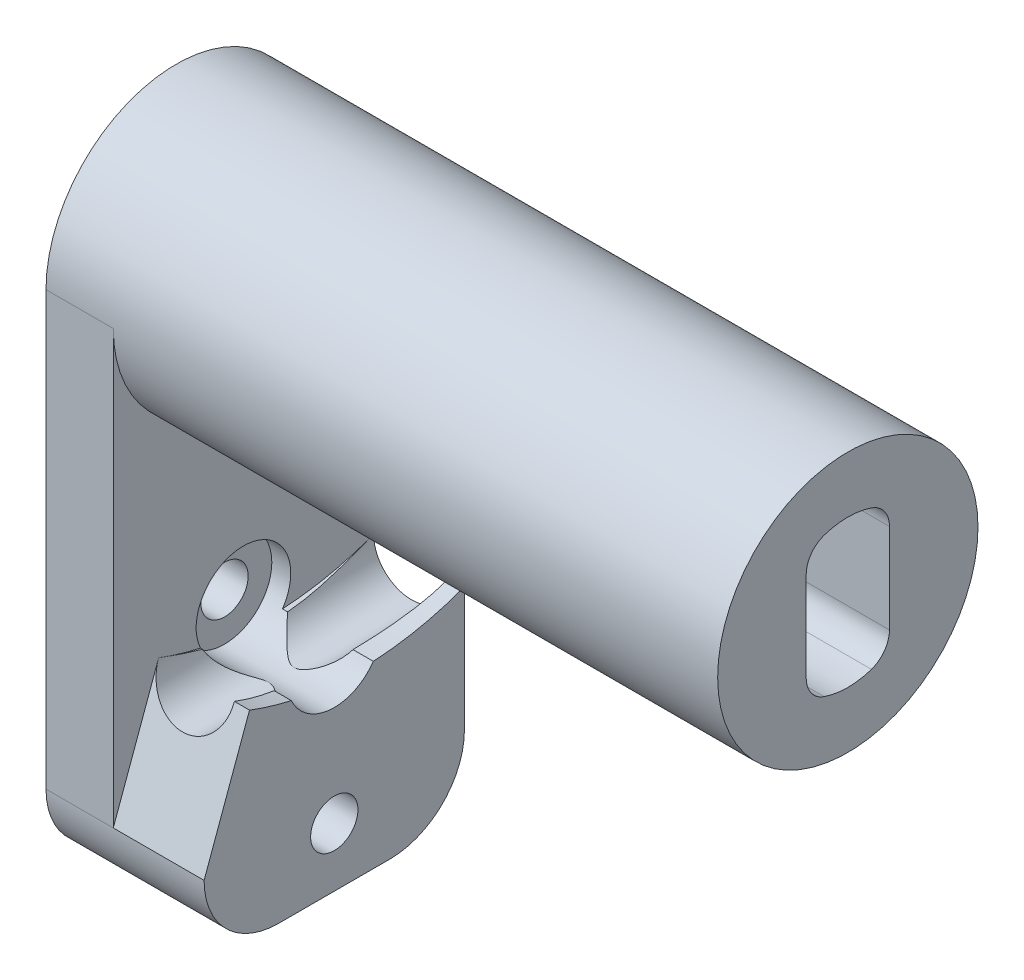
SolidWorks part; units mm, degrees
material "ABS"
ref_plane "Front Plane" through (0, 0, 0) normal (1, 0, 0) x (0, 1, 0)
ref_plane "Top Plane" through (0, 0, 0) normal (0, 0, 1) x (0, 1, 0)
ref_plane "Right Plane" through (0, 0, 0) normal (0, 1, 0) x (-1, 0, 0)
sketch "Sketch1" plane through (0, 0, 0) normal (1, 0, 0) x (0, 1, 0)
  circle A2 centre (0, 0) radius 8.7376
  dimension "D3" = 17.4752
extrude "Boss-Extrude1" add sketch "Sketch1" along normal blind 45.085 contours A2 region at (0, 0, 0)
sketch "Sketch10" plane through (0, 0, 0) normal (-1, 0, 0) x (0, -1, 0)
  line L0 (0, 8.7376) -> (34.036, 8.7376)
  line L2 (34.036, 8.7376) -> (34.036, -8.7376)
  line L3 (34.036, -8.7376) -> (0, -8.7376)
  circle A0 centre (0, 0) radius 8.7376 construction
  arc A2 (0, 8.7376) -> (0, -8.7376) centre (0, 0) cw
  dimension "D1" = 34.036
extrude "Boss-Extrude3" add sketch "Sketch10" against normal blind 4.516 contours L0 A2 L3 L2 region at (0, -20.3793, 0)
fillet "Fillet2" radius 5 2 edges at (2.258, -34.036, 8.7376) (2.258, -34.036, -8.7376)
sketch "Sketch14" [suppressed] plane through (0, 0, 0) normal (-1, 0, 0) x (0, 0, 1)
  line L0 (0.5115, -3.4237) -> (0.3944, -4.0089)
  line L1 (0, 0) -> (0, -4.064) construction
  line L2 (0, 0) -> (0.5606, -3.4335) construction
  line L3 (0.6039, -3.4087) -> (0.9011, -3.9262)
  line L4 (-0.6903, -3.3922) -> (-1.0005, -3.9021)
  line L5 (-0.5983, -3.4096) -> (-0.4961, -3.9976)
  line L6 (-1.8089, -2.9515) -> (-2.2748, -3.3245)
  line L7 (-1.7284, -2.9994) -> (-1.8334, -3.5869)
  line L8 (-2.7093, -2.1549) -> (-3.2746, -2.346)
  line L9 (-2.65, -2.2273) -> (-2.9496, -2.7435)
  line L10 (-3.2829, -1.0983) -> (-3.8795, -1.0846)
  line L11 (-3.252, -1.1867) -> (-3.7101, -1.5692)
  line L12 (-3.4605, 0.0907) -> (-4.0165, 0.3077)
  line L13 (-3.4617, -0.0029) -> (-4.023, -0.2057)
  line L14 (-3.2208, 1.2689) -> (-3.669, 1.6629)
  line L15 (-3.2539, 1.1813) -> (-3.8507, 1.1827)
  line L16 (-2.5926, 2.2939) -> (-2.879, 2.8175)
  line L17 (-2.6537, 2.223) -> (-3.214, 2.4284)
  line L18 (-1.6517, 3.0423) -> (-1.7417, 3.6323)
  line L19 (-1.7333, 2.9965) -> (-2.1896, 3.3812)
  line L20 (-0.5115, 3.4237) -> (-0.3944, 4.0089)
  line L21 (-0.6039, 3.4087) -> (-0.9011, 3.9262)
  line L22 (0.6903, 3.3922) -> (1.0005, 3.9021)
  line L23 (0.5983, 3.4096) -> (0.4961, 3.9976)
  line L24 (1.8089, 2.9515) -> (2.2748, 3.3245)
  line L25 (1.7284, 2.9994) -> (1.8334, 3.5869)
  line L26 (2.7093, 2.1549) -> (3.2746, 2.346)
  line L27 (2.65, 2.2273) -> (2.9496, 2.7435)
  line L28 (3.2829, 1.0983) -> (3.8795, 1.0846)
  line L29 (3.252, 1.1867) -> (3.7101, 1.5692)
  line L30 (3.4605, -0.0907) -> (4.0165, -0.3077)
  line L31 (3.4617, 0.0029) -> (4.023, 0.2057)
  line L32 (3.2208, -1.2689) -> (3.669, -1.6629)
  line L33 (3.2539, -1.1813) -> (3.8507, -1.1827)
  line L34 (2.5926, -2.2939) -> (2.879, -2.8175)
  line L35 (2.6537, -2.223) -> (3.214, -2.4284)
  line L36 (1.6517, -3.0423) -> (1.7417, -3.6323)
  line L37 (1.7333, -2.9965) -> (2.1896, -3.3812)
  line L38 (-0.1032, -4.0627) -> (0, -4.064)
  line L39 (-1.4865, -3.7824) -> (-1.39, -3.8189)
  line L40 (-2.6905, -3.0459) -> (-2.6123, -3.1132)
  line L41 (-3.5195, -2.032) -> (-3.57, -1.942)
  line L42 (-4.0023, -0.7057) -> (-4.0189, -0.6039)
  line L43 (-4.0023, 0.7057) -> (-3.9831, 0.8071)
  line L44 (-3.5195, 2.032) -> (-3.4668, 2.1207)
  line L45 (-2.6123, 3.1132) -> (-2.5324, 3.1785)
  line L46 (-1.39, 3.8189) -> (-1.2926, 3.853)
  line L47 (0, 4.064) -> (0.1032, 4.0627)
  line L48 (1.39, 3.8189) -> (1.4865, 3.7824)
  line L49 (2.6123, 3.1132) -> (2.6905, 3.0459)
  line L50 (3.5195, 2.032) -> (3.57, 1.942)
  line L51 (4.0023, 0.7057) -> (4.0189, 0.6039)
  line L52 (4.0023, -0.7057) -> (3.9831, -0.8071)
  line L53 (3.5195, -2.032) -> (3.4668, -2.1207)
  line L54 (2.6123, -3.1132) -> (2.5324, -3.1785)
  line L55 (1.39, -3.8189) -> (1.2926, -3.853)
  arc A0 (0.3497, -4.0489) -> (0, -4.064) centre (0, 0) cw
  arc A1 (0.3497, -4.0489) -> (0.3944, -4.0089) centre (0.3454, -3.9991) ccw
  arc A2 (0.5115, -3.4237) -> (0.6039, -3.4087) centre (0.5606, -3.4335) cw
  arc A3 (0.4203, -4.0631) -> (0.3944, -4.0089) centre (0.4434, -4.0187) cw
  arc A4 (0.4203, -4.0631) -> (0.7372, -4.2116) centre (2.3016, -0.4608) ccw
  arc A6 (0.9562, -3.9499) -> (0.9011, -3.9262) centre (0.9445, -3.9013) cw
  arc A7 (0.9562, -3.9499) -> (1.2926, -3.853) centre (0, 0) ccw
  arc A8 (-1.0562, -3.9243) -> (-1.39, -3.8189) centre (0, 0) cw
  arc A9 (-1.0562, -3.9243) -> (-1.0005, -3.9021) centre (-1.0432, -3.8761) ccw
  arc A10 (-0.6903, -3.3922) -> (-0.5983, -3.4096) centre (-0.6476, -3.4182) cw
  arc A11 (-0.4524, -4.0387) -> (-0.4961, -3.9976) centre (-0.4468, -3.9891) cw
  arc A12 (-0.4524, -4.0387) -> (-0.1032, -4.0627) centre (0, 0) ccw
  arc A13 (-2.3347, -3.3264) -> (-2.6123, -3.1132) centre (0, 0) cw
  arc A14 (-2.3347, -3.3264) -> (-2.2748, -3.3245) centre (-2.306, -3.2855) ccw
  arc A15 (-1.8089, -2.9515) -> (-1.7284, -2.9994) centre (-1.7776, -2.9906) cw
  arc A16 (-1.8064, -3.6405) -> (-1.8334, -3.5869) centre (-1.7842, -3.5957) cw
  arc A17 (-1.8064, -3.6405) -> (-1.4865, -3.7824) centre (0, 0) ccw
  arc A18 (-3.3316, -2.3273) -> (-3.5195, -2.032) centre (0, 0) cw
  arc A19 (-3.3316, -2.3273) -> (-3.2746, -2.346) centre (-3.2906, -2.2987) ccw
  arc A20 (-2.7093, -2.1549) -> (-2.65, -2.2273) centre (-2.6933, -2.2022) cw
  arc A21 (-2.9426, -2.8031) -> (-2.9496, -2.7435) centre (-2.9064, -2.7686) cw
  arc A22 (-2.9426, -2.8031) -> (-2.6905, -3.0459) centre (0, 0) ccw
  arc A23 (-3.9267, -1.0475) -> (-4.0023, -0.7057) centre (0, 0) cw
  arc A24 (-3.9267, -1.0475) -> (-3.8795, -1.0846) centre (-3.8784, -1.0346) ccw
  arc A25 (-3.2829, -1.0983) -> (-3.252, -1.1867) centre (-3.284, -1.1483) cw
  arc A26 (-3.7238, -1.6276) -> (-3.7101, -1.5692) centre (-3.678, -1.6076) cw
  arc A27 (-3.7238, -1.6276) -> (-3.57, -1.942) centre (0, 0) ccw
  arc A28 (-4.0481, 0.3587) -> (-4.0023, 0.7057) centre (0, 0) cw
  arc A29 (-4.0481, 0.3587) -> (-4.0165, 0.3077) centre (-3.9983, 0.3543) ccw
  arc A30 (-3.4605, 0.0907) -> (-3.4617, -0.0029) centre (-3.4787, 0.0442) cw
  arc A31 (-4.0559, -0.2558) -> (-4.023, -0.2057) centre (-4.006, -0.2527) cw
  arc A32 (-4.0559, -0.2558) -> (-4.0189, -0.6039) centre (0, 0) ccw
  arc A33 (-3.6813, 1.7216) -> (-3.5195, 2.032) centre (0, 0) cw
  arc A34 (-3.6813, 1.7216) -> (-3.669, 1.6629) centre (-3.636, 1.7005) ccw
  arc A35 (-3.2208, 1.2689) -> (-3.2539, 1.1813) centre (-3.2538, 1.2313) cw
  arc A36 (-3.8988, 1.1468) -> (-3.8507, 1.1827) centre (-3.8509, 1.1327) cw
  arc A37 (-3.8988, 1.1468) -> (-3.9831, 0.8071) centre (0, 0) ccw
  arc A38 (-2.8705, 2.8769) -> (-2.6123, 3.1132) centre (0, 0) cw
  arc A39 (-2.8705, 2.8769) -> (-2.879, 2.8175) centre (-2.8352, 2.8415) ccw
  arc A40 (-2.5926, 2.2939) -> (-2.6537, 2.223) centre (-2.6365, 2.2699) cw
  arc A41 (-3.2715, 2.4111) -> (-3.214, 2.4284) centre (-3.2312, 2.3815) cw
  arc A42 (-3.2715, 2.4111) -> (-3.4668, 2.1207) centre (0, 0) ccw
  arc A43 (-1.7134, 3.6852) -> (-1.39, 3.8189) centre (0, 0) cw
  arc A44 (-1.7134, 3.6852) -> (-1.7417, 3.6323) centre (-1.6923, 3.6398) ccw
  arc A45 (-1.6517, 3.0423) -> (-1.7333, 2.9965) centre (-1.7011, 3.0348) cw
  arc A46 (-2.2495, 3.3846) -> (-2.1896, 3.3812) centre (-2.2218, 3.343) cw
  arc A47 (-2.2495, 3.3846) -> (-2.5324, 3.1785) centre (0, 0) ccw
  arc A48 (-0.3497, 4.0489) -> (0, 4.064) centre (0, 0) cw
  arc A49 (-0.3497, 4.0489) -> (-0.3944, 4.0089) centre (-0.3454, 3.9991) ccw
  arc A50 (-0.5115, 3.4237) -> (-0.6039, 3.4087) centre (-0.5606, 3.4335) cw
  arc A51 (-0.9562, 3.9499) -> (-0.9011, 3.9262) centre (-0.9445, 3.9013) cw
  arc A52 (-0.9562, 3.9499) -> (-1.2926, 3.853) centre (0, 0) ccw
  arc A53 (1.0562, 3.9243) -> (1.39, 3.8189) centre (0, 0) cw
  arc A54 (1.0562, 3.9243) -> (1.0005, 3.9021) centre (1.0432, 3.8761) ccw
  arc A55 (0.6903, 3.3922) -> (0.5983, 3.4096) centre (0.6476, 3.4182) cw
  arc A56 (0.4524, 4.0387) -> (0.4961, 3.9976) centre (0.4468, 3.9891) cw
  arc A57 (0.4524, 4.0387) -> (0.1032, 4.0627) centre (0, 0) ccw
  arc A58 (2.3347, 3.3264) -> (2.6123, 3.1132) centre (0, 0) cw
  arc A59 (2.3347, 3.3264) -> (2.2748, 3.3245) centre (2.306, 3.2855) ccw
  arc A60 (1.8089, 2.9515) -> (1.7284, 2.9994) centre (1.7776, 2.9906) cw
  arc A61 (1.8064, 3.6405) -> (1.8334, 3.5869) centre (1.7842, 3.5957) cw
  arc A62 (1.8064, 3.6405) -> (1.4865, 3.7824) centre (0, 0) ccw
  arc A63 (3.3316, 2.3273) -> (3.5195, 2.032) centre (0, 0) cw
  arc A64 (3.3316, 2.3273) -> (3.2746, 2.346) centre (3.2906, 2.2987) ccw
  arc A65 (2.7093, 2.1549) -> (2.65, 2.2273) centre (2.6933, 2.2022) cw
  arc A66 (2.9426, 2.8031) -> (2.9496, 2.7435) centre (2.9064, 2.7686) cw
  arc A67 (2.9426, 2.8031) -> (2.6905, 3.0459) centre (0, 0) ccw
  arc A68 (3.9267, 1.0475) -> (4.0023, 0.7057) centre (0, 0) cw
  arc A69 (3.9267, 1.0475) -> (3.8795, 1.0846) centre (3.8784, 1.0346) ccw
  arc A70 (3.2829, 1.0983) -> (3.252, 1.1867) centre (3.284, 1.1483) cw
  arc A71 (3.7238, 1.6276) -> (3.7101, 1.5692) centre (3.678, 1.6076) cw
  arc A72 (3.7238, 1.6276) -> (3.57, 1.942) centre (0, 0) ccw
  arc A73 (4.0481, -0.3587) -> (4.0023, -0.7057) centre (0, 0) cw
  arc A74 (4.0481, -0.3587) -> (4.0165, -0.3077) centre (3.9983, -0.3543) ccw
  arc A75 (3.4605, -0.0907) -> (3.4617, 0.0029) centre (3.4787, -0.0442) cw
  arc A76 (4.0559, 0.2558) -> (4.023, 0.2057) centre (4.006, 0.2527) cw
  arc A77 (4.0559, 0.2558) -> (4.0189, 0.6039) centre (0, 0) ccw
  arc A78 (3.6813, -1.7216) -> (3.5195, -2.032) centre (0, 0) cw
  arc A79 (3.6813, -1.7216) -> (3.669, -1.6629) centre (3.636, -1.7005) ccw
  arc A80 (3.2208, -1.2689) -> (3.2539, -1.1813) centre (3.2538, -1.2313) cw
  arc A81 (3.8988, -1.1468) -> (3.8507, -1.1827) centre (3.8509, -1.1327) cw
  arc A82 (3.8988, -1.1468) -> (3.9831, -0.8071) centre (0, 0) ccw
  arc A83 (2.8705, -2.8769) -> (2.6123, -3.1132) centre (0, 0) cw
  arc A84 (2.8705, -2.8769) -> (2.879, -2.8175) centre (2.8352, -2.8415) ccw
  arc A85 (2.5926, -2.2939) -> (2.6537, -2.223) centre (2.6365, -2.2699) cw
  arc A86 (3.2715, -2.4111) -> (3.214, -2.4284) centre (3.2312, -2.3815) cw
  arc A87 (3.2715, -2.4111) -> (3.4668, -2.1207) centre (0, 0) ccw
  arc A88 (1.7134, -3.6852) -> (1.39, -3.8189) centre (0, 0) cw
  arc A89 (1.7134, -3.6852) -> (1.7417, -3.6323) centre (1.6923, -3.6398) ccw
  arc A90 (1.6517, -3.0423) -> (1.7333, -2.9965) centre (1.7011, -3.0348) cw
  arc A91 (2.2495, -3.3846) -> (2.1896, -3.3812) centre (2.2218, -3.343) cw
  arc A92 (2.2495, -3.3846) -> (2.5324, -3.1785) centre (0, 0) ccw
  point P207 (0, 0)
  dimension "D1" = 4.064
  dimension "D2" = 0.05
  dimension "D3" = 0.05
  dimension "D4" = 0.04
  dimension "D5" = 18
  dimension "D6" = 0.5968
  dimension "D8" = 0.35
sketch "Sketch15" plane through (4.516, 0, 0) normal (1, 0, 0) x (0, 1, 0)
  line L1 (-29.036, 8.7376) -> (-20.066, 5.4728)
  line L2 (-20.066, 5.4728) -> (-20.066, -8.7376)
  line L5 (-34.036, 3.7376) -> (-34.036, -3.7376) construction
  line L6 (-34.036, 3.7376) -> (-34.036, -3.7376)
  line L9 (-29.036, -8.7376) -> (0, -8.7376) construction
  line L13 (0, 8.7376) -> (-29.036, 8.7376)
  line L14 (-34.036, 3.7376) -> (-34.036, -3.7376)
  line L15 (-29.036, -8.7376) -> (0, -8.7376)
  line L17 (-34.036, 3.7376) -> (-34.036, -3.7376)
  line L18 (-29.036, -8.7376) -> (-20.066, -8.7376)
  arc A0 (-29.036, 8.7376) -> (-34.036, 3.7376) centre (-29.036, 3.7376) ccw construction
  arc A1 (-34.036, -3.7376) -> (-29.036, -8.7376) centre (-29.036, -3.7376) ccw construction
  arc A2 (-29.036, 8.7376) -> (-34.036, 3.7376) centre (-29.036, 3.7376) ccw
  arc A3 (-34.036, -3.7376) -> (-29.036, -8.7376) centre (-29.036, -3.7376) ccw
  arc A7 (-29.036, 8.7376) -> (-34.036, 3.7376) centre (-29.036, 3.7376) ccw
  arc A8 (-34.036, -3.7376) -> (-29.036, -8.7376) centre (-29.036, -3.7376) ccw
  arc A9 (0, 8.7376) -> (0, -8.7376) centre (0, 0) ccw
  arc A10 (-29.036, 8.7376) -> (-34.036, 3.7376) centre (-29.036, 3.7376) ccw
  arc A11 (-34.036, -3.7376) -> (-29.036, -8.7376) centre (-29.036, -3.7376) ccw
  arc A12 (0, 8.7376) -> (0, -8.7376) centre (0, 0) ccw
  line M2 (0, 8.7376) -> (-29.036, 8.7376)
  arc M3 (-29.036, 8.7376) -> (-34.036, 3.7376) centre (-29.036, 3.7376) ccw
  line M4 (-34.036, 3.7376) -> (-34.036, -3.7376)
  arc M5 (-34.036, -3.7376) -> (-29.036, -8.7376) centre (-29.036, -3.7376) ccw
  dimension "D1" = 13.97
  dimension "D3" = 20
  dimension "D2" = 0
extrude "Boss-Extrude4" add sketch "Sketch15" along normal blind 6.096 contours M2 M3 M4 M5 region at (4.516, -27.0306, -0.512)
sketch "Sketch21" plane through (10.612, 0, 0) normal (1, 0, 0) x (0, 1, 0)
  line L2 (-20.066, -8.7376) -> (-20.066, 5.4728)
  line L4 (-29.036, 8.7376) -> (-20.066, 5.4728) construction
  line L5 (-20.701, -8.7376) -> (-20.066, -8.7376)
  line L6 (-20.066, 5.4728) -> (-20.066, -8.7376) construction
  line L7 (-29.036, -8.7376) -> (-20.066, -8.7376) construction
  line L14 (-20.066, -8.7376) -> (-20.066, 5.4728) construction
  line L20 (-20.066, 5.4728) -> (-29.036, 8.7376)
  arc A2 (-20.701, -8.7376) -> (-20.6627, 5.69) centre (-1.6855, -1.5742) cw
  point P2 (0, 0)
  point P11 (-29.036, 8.7376)
  dimension "D4" = 20.32
  dimension "D2" = 0.635
  dimension "D3" = 0.635
extrude "Cut-Extrude8" cut sketch "Sketch21" against normal up to surface (6.096 mm away) up to face at (4.516, -15.5811, 1.0946)
sketch "Sketch22" plane through (45.085, 0, 0) normal (1, 0, 0) x (0, 1, 0)
  line L7 (-4.0897, -2.794) -> (4.0897, 2.794) construction
  line L8 (-4.0897, 2.794) -> (4.0897, -2.794) construction
  line L11 (-4.0897, -2.794) -> (4.0897, -2.794)
  line L13 (-4.0897, 2.794) -> (4.0897, 2.794)
  line L15 (-4.0897, -2.794) -> (4.0897, 2.794) construction
  line L16 (-4.0897, 2.794) -> (4.0897, -2.794) construction
  arc A3 (-4.0897, 2.794) -> (-4.0897, -2.794) centre (0, 0) ccw
  arc A4 (4.0897, -2.794) -> (4.0897, 2.794) centre (0, 0) ccw
  dimension "D2" = 9.906
  dimension "D3" = 5.588
extrude "Cut-Extrude10" cut sketch "Sketch22" against normal blind 12.192
sketch "Sketch23" plane through (0, 0, 0) normal (-1, 0, 0) x (0, 0, 1)
  line L0 (0, -33.5187) -> (0, 0) construction
  line L2 (0, -30.0897) -> (0, -20.1843) construction
  line L3 (0, -20.1843) -> (0, -10.279) construction
  line L6 (-3.7376, -33.5187) -> (3.7376, -33.5187)
  line L7 (8.2296, -29.0267) -> (8.2296, 0)
  line L8 (-8.2296, 0) -> (-8.2296, -29.0267)
  arc A6 (-8.2296, -29.0267) -> (-3.7376, -33.5187) centre (-3.7376, -29.0267) ccw
  arc A7 (3.7376, -33.5187) -> (8.2296, -29.0267) centre (3.7376, -29.0267) ccw
  arc A8 (8.2296, 0) -> (-8.2296, 0) centre (0, 0) ccw
  circle A9 centre (0, -30.0897) radius 1.5875
  circle A10 centre (0, -20.1843) radius 1.5875
  dimension "D1" = 3.175
  dimension "D3" = 4.492
  dimension "D5" = 8.2296
  dimension "D2" = 9.9054
  dimension "D4" = 29.0267
  dimension "D6" = 3.429
extrude "Cut-Extrude11" cut sketch "Sketch23" against normal through all contours A10 | A9 region at (0, -30.0897, 0) region at (0, -20.1843, 0)
sketch "Sketch24" plane through (4.516, 0, 0) normal (1, 0, 0) x (0, 1, 0)
  circle A0 centre (-20.1843, 0) radius 1.5875 construction
  circle A1 centre (-20.1843, 0) radius 1.5875
  circle A2 centre (-20.1843, 0) radius 3.175
  dimension "D1" = 6.35
extrude "Cut-Extrude12" cut sketch "Sketch24" along normal through all
extrude "Cut-Extrude13" cut sketch "Sketch24<2>" against normal blind 1.27
sketch "Sketch24<2>" plane through (4.516, 0, 0) normal (1, 0, 0) x (0, 1, 0) same geometry as "Sketch24"
fillet "Fillet11" radius 1.778 4 edges at (38.989, 4.0897, -2.794) (38.989, 4.0897, 2.794) (38.989, -4.0897, -2.794) (38.989, -4.0897, 2.794)
sketch "Sketch25" plane through (0, 0, -8.7376) normal (0, 0, -1) x (1, 0, 0)
  line L3 (4.516, 20.701) -> (4.516, 0) construction
  line L4 (4.516, 20.701) -> (10.612, 20.701) construction
  circle A0 centre (7.056, 20.701) radius 2.54
  point P2 (7.056, 21.6969)
  point P3 (7.056, 20.701)
  point P4 (5.056, 20.066)
  point P5 (0, 0)
  point P9 (0, 0)
  dimension "D1" = 5.08
extrude "Cut-Extrude14" cut sketch "Sketch25" against normal through all
